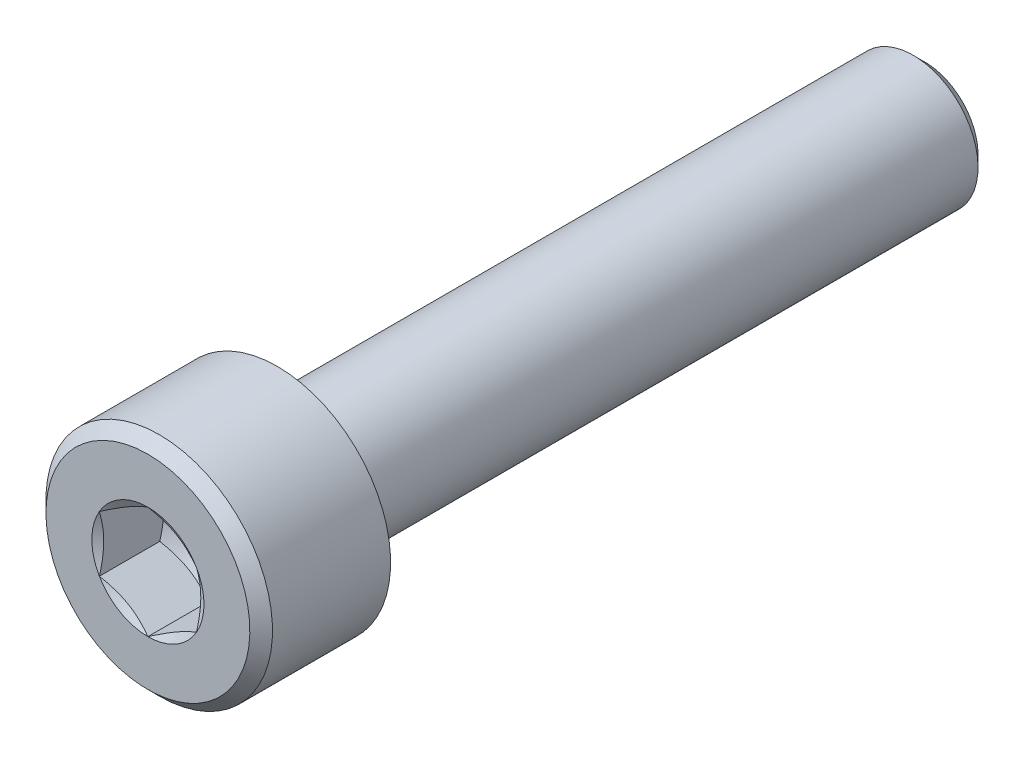
SolidWorks part; units mm, degrees
material "Chrome Stainless Steel"
ref_plane "Front" through (0, 0, 0) normal (0, 0, 1) x (1, 0, 0)
ref_plane "Top" through (0, 0, 0) normal (0, 1, 0) x (1, 0, 0)
ref_plane "Right" through (0, 0, 0) normal (1, 0, 0) x (0, 0, -1)
sketch "Sketch1" plane through (0, 0, 0) normal (1, 0, 0) x (0, 0, -1)
  line L0 (0, 3.5) -> (-4, 3.5)
  line L1 (-4, 3.5) -> (-4, 0)
  line L2 (-4, 0) -> (20, 0)
  line L3 (20, 0) -> (20, 2)
  line L4 (20, 2) -> (0, 2)
  line L5 (0, 2) -> (0, 3.5)
  line L6 (0, 0) -> (12.7561, 0) construction
  dimension "l" = 20
  dimension "d" = 4
  dimension "k" = 4
  dimension "dk" = 7
revolve "Revolve1" add sketch "Sketch1" angle 360 about L2
sketch "Sketch7" plane through (0, 0, 0) normal (1, 0, 0) x (0, 0, -1)
  line L0 (-6.6396, 0) -> (3.6195, 0) construction
  line L1 (-4, 0) -> (-4, 1.5)
  line L2 (-4, 3.5) -> (-4, -3.5) construction
  line L3 (-4, 1.5) -> (-2, 1.5)
  line L4 (-2, 1.5) -> (-1.134, 0)
  line L6 (-4, 0) -> (-1.134, 0)
  dimension "D1" = 60
  dimension "S" = 3
  dimension "t" = 2
revolve "Cut-Revolve2" cut sketch "Sketch7" angle 360 about L6
chamfer "Chamfer1" distance 0.35 2 edges at (0, -2, -20) (0, -3.5, 4)
sketch "Sketch8" plane through (0, 0, 4) normal (0, 0, 1) x (1, 0, 0)
  line L1 (0, 1.7321) -> (-1.5, 0.866)
  line L2 (-1.5, 0.866) -> (-1.5, -0.866)
  line L3 (-1.5, -0.866) -> (0, -1.7321)
  line L4 (0, -1.7321) -> (1.5, -0.866)
  line L5 (1.5, -0.866) -> (1.5, 0.866)
  line L6 (1.5, 0.866) -> (0, 1.7321)
  circle A0 centre (0, 0) radius 1.5 construction
  circle A1 centre (0, 0) radius 1.5 construction
extrude "Cut-Extrude1" cut sketch "Sketch8" against normal up to surface (1.866 mm away) up to face at (1.5, 0, 2)
sketch "Sketch9" plane through (0, 0, 0) normal (1, 0, 0) x (0, 0, -1)
  line L0 (-4, 1.5) -> (4.2695, 1.5) construction
  line L3 (-4.5, 2.5981) -> (-4.5, 1.5)
  line L4 (-4.5, 1.5) -> (-3.866, 1.5)
  line L5 (-3.866, 1.5) -> (-4.5, 2.5981)
  line L6 (-4, 3.5) -> (-4, -3.5) construction
  dimension "D1" = 60
  dimension "D2" = 0.5
revolve "Cut-Revolve3" cut sketch "Sketch9" angle 360 about axis through (0, 0, 4) along (0, 0, -1)
fillet "Fillet2" radius 0.4 1 edges at (0, -2, 0)
